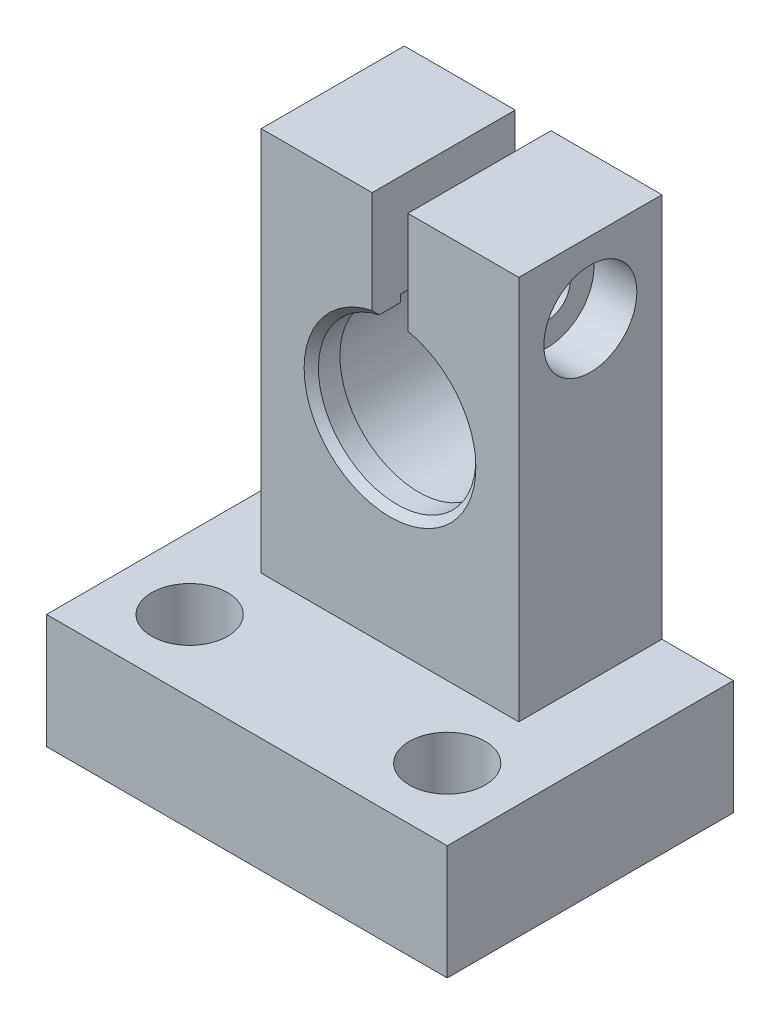
SolidWorks part; units mm, degrees
material "AISI 1045 Steel, cold drawn"
ref_plane "Front Plane" through (0, 0, 0) normal (0, 0, 1) x (1, 0, 0)
ref_plane "Top Plane" through (0, 0, 0) normal (0, 1, 0) x (1, 0, 0)
ref_plane "Right Plane" through (0, 0, 0) normal (1, 0, 0) x (0, 0, -1)
sketch "Sketch1" plane through (0, 0, 0) normal (0, 0, 1) x (1, 0, 0)
  line L1 (9, -21.9) -> (-9, -21.9)
  line L2 (9, -21.9) -> (9, 13)
  line L3 (9, 13) -> (-9, 13)
  line L4 (-9, -21.9) -> (-9, 13)
  line L5 (9, -21.9) -> (-9, 13) construction
  line L6 (9, 13) -> (-9, -21.9) construction
  circle A0 centre (0, 0) radius 6
  point P3 (0, -4.45)
  dimension "D1" = 12
  dimension "D2" = 13
  dimension "D3" = 21.9
  dimension "D4" = 18
extrude "Boss-Extrude1" add sketch "Sketch1" along normal blind 10
sketch "Sketch2" plane through (0, 0, 10) normal (0, 0, -1) x (-1, 0, 0)
  circle A0 centre (0, 0) radius 6 construction
  circle A1 centre (0, 0) radius 6
  circle A2 centre (0, 0) radius 5.5
  dimension "D1" = 0.5
extrude "Boss-Extrude2" add sketch "Sketch2" along normal blind 2
sketch "Sketch3" plane through (0, 0, 10) normal (0, 0, 1) x (1, 0, 0)
  line L0 (9, 13) -> (-9, 13) construction
  line L1 (1.25, 5.3561) -> (-1.25, 5.3561)
  line L2 (1.25, 5.3561) -> (1.25, 13)
  line L3 (1.25, 13) -> (-1.25, 13)
  line L4 (-1.25, 5.3561) -> (-1.25, 13)
  line L5 (1.25, 5.3561) -> (-1.25, 13) construction
  line L6 (1.25, 13) -> (-1.25, 5.3561) construction
  circle A0 centre (0, 0) radius 5.5 construction
  point P0 (0, 9.178)
  dimension "D1" = 2.5
extrude "Cut-Extrude1" cut sketch "Sketch3" against normal through all
hole_wizard "CBORE for M3 SHCS1" positions "Sketch4" profile "Sketch5" counterbore size "M3" standard "ANSI Metric" end condition up to next
sketch "Sketch4" plane through (9, 0, 0) normal (1, 0, 0) x (0, 0, -1)
  line L0 (0, -21.9) -> (0, 13) construction
  line L1 (-10, 13) -> (0, 13) construction
  point P0 (-5, 8)
  dimension "D1" = 5
  dimension "D2" = 5
sketch "Sketch5" plane through (9, 8, 5) normal (0, 1, 0) x (0, 0, -1)
  line L0 (0, 0) -> (0, 7.75)
  line L1 (0, 7.75) -> (1.6, 7.75)
  line L3 (1.6, 7.75) -> (1.6, 3)
  line L4 (1.6, 3) -> (3.25, 3)
  line L5 (3.25, 3) -> (3.25, 0)
  line L7 (3.25, 0) -> (0, 0)
  line L11 (0, -6.35) -> (0, 107.95) construction
  dimension "Thru Hole Dia." = 3.2
  dimension "Thru Hole Depth" = 7.75
  dimension "C'Bore Dia." = 6.5
  dimension "C'Bore Depth" = 3
hole_wizard "Tap Drill for M3x0.5 Tap1" positions "Sketch6" profile "Sketch7" hole size "M3x0.5" standard "ANSI Metric" end condition up to next
sketch "Sketch6" plane through (-9, 0, 0) normal (-1, 0, 0) x (0, 0, 1)
  line L0 (10, 13) -> (10, -21.9) construction
  line L1 (10, 13) -> (0, 13) construction
  point P0 (5, 8)
  dimension "D1" = 5
  dimension "D2" = 5
sketch "Sketch7" plane through (-9, 8, 5) normal (0, 1, 0) x (0, 0, 1)
  line L0 (0, 0) -> (0, 7.75)
  line L1 (0, 7.75) -> (1.25, 7.75)
  line L2 (1.25, 7.75) -> (1.25, 0)
  line L5 (1.25, 0) -> (0, 0)
  line L11 (0, -6.35) -> (0, 107.95) construction
  dimension "Thru Hole Dia." = 2.5
  dimension "Thru Hole Depth" = 7.75
chamfer "Chamfer1" distance 0.5 angle 45 2 edges at (0, -5.5, 10) (0, -6, 0)
sketch "Sketch11" plane through (-9, 0, 0) normal (-1, 0, 0) x (0, 0, 1)
  line L0 (0, 13) -> (0, -21.9) construction
  line L1 (0, -21.9) -> (10, -21.9)
  line L2 (0, -21.9) -> (0, -13.9)
  line L3 (0, -13.9) -> (10, -13.9)
  line L4 (10, -21.9) -> (10, -13.9)
  line L5 (10, 13) -> (10, -21.9) construction
  point P8 (0, -21.9)
  point P9 (10, -21.9)
  point P10 (0, -21.9)
  dimension "D1" = 8
extrude "Boss-Extrude4" add sketch "Sketch11" along normal blind 5
mirror "Mirror1" about plane through (0, 0, 0) normal (1, 0, 0) of "Boss-Extrude4"
sketch "Sketch8" plane through (0, -21.9, 0) normal (0, -1, 0) x (1, 0, 0)
  line L0 (-14, 0) -> (-14, 10) construction
  line L1 (-14, 10) -> (14, 10)
  line L2 (-14, 10) -> (-14, 20)
  line L3 (-14, 20) -> (14, 20)
  line L4 (14, 10) -> (14, 20)
  point P5 (14, 10)
  point P8 (-14, 10)
  dimension "D1" = 10
extrude "Boss-Extrude3" add sketch "Sketch8" against normal up to surface (8 mm away) up to face at (-11.5, -13.9, 5)
hole_wizard "M5 Clearance Hole1" positions "Sketch9" profile "Sketch10" hole size "M5" standard "ANSI Metric" end condition up to next
sketch "Sketch9" plane through (0, -13.9, 0) normal (0, 1, 0) x (1, 0, 0)
  line L0 (14, -20) -> (-14, -20) construction
  line L1 (-14, -20) -> (-14, 0) construction
  line L2 (0, -10) -> (0, -20) construction
  line L4 (-9, -10) -> (9, -10) construction
  point P0 (-9, -15)
  point P14 (9, -15)
  dimension "D1" = 5
  dimension "D2" = 5
sketch "Sketch10" plane through (-9, -13.9, 15) normal (1, 0, 0) x (0, 0, 1)
  line L0 (0, 0) -> (0, 8)
  line L1 (0, 8) -> (2.65, 8)
  line L2 (2.65, 8) -> (2.65, 0)
  line L5 (2.65, 0) -> (0, 0)
  line L11 (0, -6.35) -> (0, 107.95) construction
  dimension "Thru Hole Dia." = 5.3
  dimension "Thru Hole Depth" = 8
